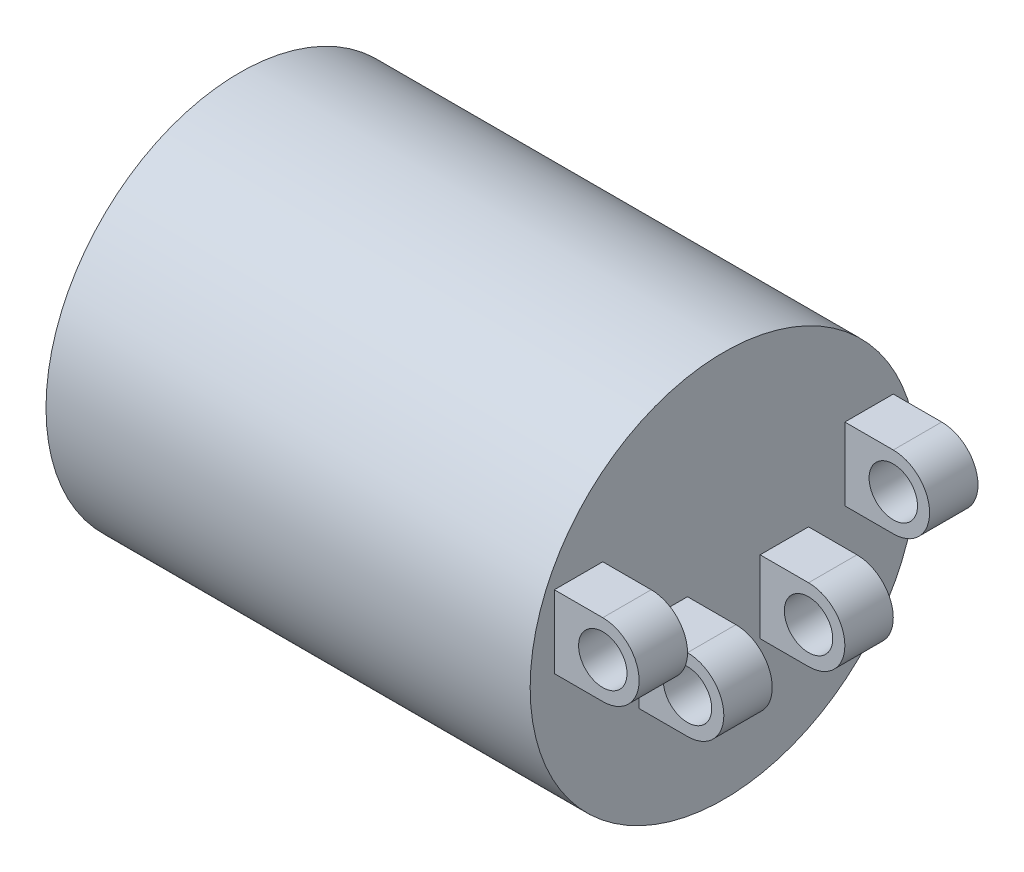
SolidWorks part; units mm, degrees
ref_plane "前视基准面" through (0, 0, 0) normal (0, 0, 1) x (1, 0, 0)
ref_plane "上视基准面" through (0, 0, 0) normal (0, 1, 0) x (1, 0, 0)
ref_plane "右视基准面" through (0, 0, 0) normal (1, 0, 0) x (0, 0, -1)
sketch "草图1" plane through (0, 0, 0) normal (1, 0, 0) x (0, 0, -1)
  circle A0 centre (0, 0) radius 40
extrude "凸台-拉伸1" add sketch "草图1" against normal blind 50 and the other way blind 50
sketch "草图2" plane through (50, 0, 0) normal (1, 0, 0) x (0, 0, -1)
  line L0 (-1000, 0) -> (49000, 0) construction
  line L1 (0, -1000) -> (0, 15) construction
  line L2 (-25, 0) -> (-25, 15)
  line L3 (25, 0) -> (25, 15)
  line L4 (7.5, -15) -> (7.5, 0)
  line L5 (-7.5, -15) -> (-7.5, 0)
  line L6 (7.5, -15) -> (17.5, -15)
  line L7 (-25, 15) -> (-35, 15)
  line L8 (-17.5, -15) -> (-7.5, -15)
  line L9 (-35, 15) -> (-25, 15)
  line L10 (-25, 15) -> (-25, 0)
  line L11 (-25, 0) -> (-35, 0)
  line L12 (-35, 15) -> (-35, 0)
  line L13 (25, 15) -> (35, 15)
  line L14 (25, 15) -> (25, 0)
  line L15 (25, 0) -> (35, 0)
  line L16 (35, 15) -> (35, 0)
  line L17 (-7.5, 0) -> (-17.5, 0)
  line L18 (-7.5, 0) -> (-7.5, -15)
  line L19 (-7.5, -15) -> (-17.5, -15)
  line L20 (-17.5, 0) -> (-17.5, -15)
  line L21 (7.5, 0) -> (17.5, 0)
  line L22 (7.5, 0) -> (7.5, -15)
  line L23 (7.5, -15) -> (17.5, -15)
  line L24 (17.5, 0) -> (17.5, -15)
  line L25 (-1000, -15) -> (49000, -15) construction
  line L26 (-1000, 15) -> (49000, 15) construction
  line L27 (-25, -1000) -> (-25, 49000) construction
  line L28 (25, -1000) -> (25, 49000) construction
  line L29 (7.5, -1000) -> (7.5, 49000) construction
  line L30 (-7.5, -1000) -> (-7.5, 49000) construction
  line L31 (25, 15) -> (35, 15)
  line L32 (0, -1000) -> (0, 49000) construction
  point P4 (0, 0)
  point P35 (0, 0)
  dimension "D1" = 25
  dimension "D2" = 25
  dimension "D3" = 7.5
  dimension "D4" = 7.5
  dimension "D7" = 15
  dimension "D8" = 15
extrude "凸台-拉伸2" add sketch "草图2" along normal blind 10 separate body contours L16 L13 L3 L15 | L24 L21 L4 L6 | L17 L20 L8 L5 | L7 L12 L11 L2 region at (50, 7.5, 30) region at (50, 7.5, -30) region at (50, -7.5, -12.5) region at (50, -7.5, 12.5)
sketch "草图3" plane through (60, 0, 0) normal (1, 0, 0) x (0, 0, -1)
  line L0 (-25, 0) -> (-25, 15) construction
  line L1 (-35, 0) -> (-25, 0)
  line L2 (-35, 0) -> (-35, 7.5)
  line L3 (-35, 7.5) -> (-25, 7.5)
  line L4 (-25, 0) -> (-25, 7.5)
revolve "旋转1" add sketch "草图3" angle 180 about L3 reverse direction yes
sketch "草图4" plane through (60, 0, 0) normal (1, 0, 0) x (0, 0, -1)
  line L0 (35, 15) -> (35, 0) construction
  line L1 (25, 0) -> (35, 0)
  line L2 (25, 0) -> (25, 7.5)
  line L3 (25, 7.5) -> (35, 7.5)
  line L4 (35, 0) -> (35, 7.5)
revolve "旋转2" add sketch "草图4" angle 180 about L3 reverse direction yes
sketch "草图5" plane through (60, 0, 0) normal (1, 0, 0) x (0, 0, -1)
  line L0 (-7.5, -15) -> (-7.5, 0) construction
  line L1 (-17.5, -15) -> (-7.5, -15)
  line L2 (-17.5, -15) -> (-17.5, -7.5)
  line L3 (-17.5, -7.5) -> (-7.5, -7.5)
  line L4 (-7.5, -15) -> (-7.5, -7.5)
revolve "旋转3" add sketch "草图5" angle 180 about L3 reverse direction yes
sketch "草图6" plane through (60, 0, 0) normal (1, 0, 0) x (0, 0, -1)
  line L0 (17.5, 0) -> (17.5, -15) construction
  line L1 (7.5, -15) -> (17.5, -15)
  line L2 (7.5, -15) -> (7.5, -7.5)
  line L3 (7.5, -7.5) -> (17.5, -7.5)
  line L4 (17.5, -15) -> (17.5, -7.5)
revolve "旋转4" add sketch "草图6" angle 180 about L3 reverse direction yes
sketch "草图7" plane through (0, 0, 35) normal (0, 0, 1) x (1, 0, 0)
  circle A0 centre (60, 7.5) radius 5
extrude "切除-拉伸1" cut sketch "草图7" against normal up to surface (70 mm away) up to face at (56.875, 7.5, -35)
sketch "草图8" plane through (0, 0, 17.5) normal (0, 0, 1) x (1, 0, 0)
  circle A0 centre (60, -7.5) radius 5
extrude "切除-拉伸2" cut sketch "草图8" against normal up to surface (35 mm away) up to face at (56.875, -7.5, -17.5)
